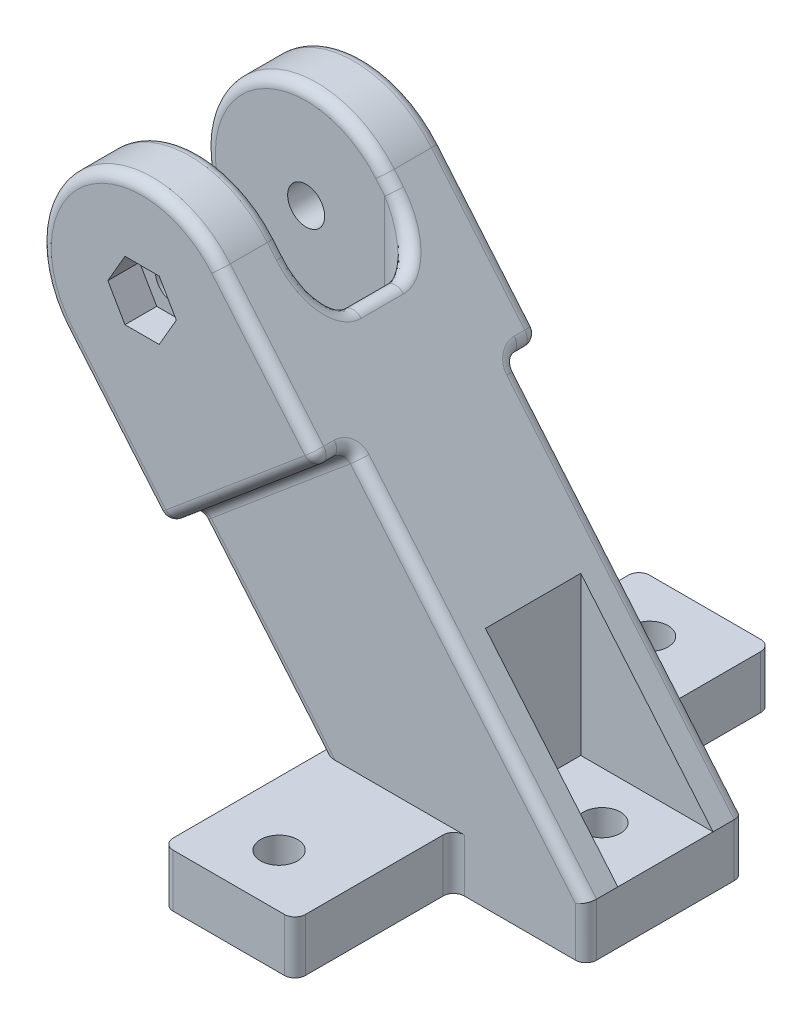
SolidWorks part; units mm, degrees
ref_plane "Alzado" through (0, 0, 0) normal (0, 0, 1) x (1, 0, 0)
ref_plane "Planta" through (0, 0, 0) normal (0, 1, 0) x (1, 0, 0)
ref_plane "Vista lateral" through (0, 0, 0) normal (1, 0, 0) x (0, 0, -1)
sketch "Croquis1" plane through (0, 0, 0) normal (0, 0, 1) x (1, 0, 0)
  line L4 (-12.5, 0) -> (12.5, 0)
  line L5 (-12.5, 0) -> (-12.5, 5)
  line L7 (12.5, 5) -> (12.5, 0)
  line L8 (-12.5, 5) -> (-50.2595, 50)
  line L9 (-50.2595, 50) -> (-25.2595, 50)
  line L10 (-25.2595, 50) -> (12.5, 5)
  line L11 (-12.5, 5) -> (-25.1154, 5) construction
  point P3 (0, 0)
  dimension "D1" = 25
  dimension "D2" = 5
  dimension "D3" = 50
  dimension "D4" = 50
  dimension "D5" = 25
extrude "Saliente-Extruir1" add sketch "Croquis1" along normal mid plane 45
sketch "Croquis3" plane through (0, 0, 0) normal (0, -1, 0) x (1, 0, 0)
  line L0 (-6.5, 0) -> (6.5, 0) construction
  line L1 (-6.5, 17.5) -> (-6.5, -17.5) construction
  circle A0 centre (-6.5, 17.5) radius 1.75
  circle A1 centre (6.5, 0) radius 1.75
  circle A2 centre (-6.5, -17.5) radius 1.75
  point P3 (0, 0)
  dimension "D3" = 3.5
  dimension "D1" = 13
  dimension "D2" = 35
extrude "Cortar-Extruir2" cut sketch "Croquis3" against normal through all
sketch "Croquis4" plane through (0, 0, 0) normal (0, -1, 0) x (1, 0, 0)
  line L0 (-12.5, 22.5) -> (12.5, 22.5) construction
  line L1 (12.5, 22.5) -> (0, 22.5)
  line L2 (12.5, 22.5) -> (12.5, 7.5)
  line L3 (12.5, 7.5) -> (0, 7.5)
  line L4 (0, 22.5) -> (0, 7.5)
  line L5 (12.5, -22.5) -> (0, -22.5)
  line L6 (12.5, -22.5) -> (12.5, -7.5)
  line L7 (12.5, -7.5) -> (0, -7.5)
  line L8 (0, -22.5) -> (0, -7.5)
  line L9 (0, 0) -> (12.5, 0) construction
  line L10 (12.5, 22.5) -> (12.5, -22.5) construction
  point P15 (0, 22.5)
  dimension "D1" = 7.5
extrude "Cortar-Extruir3" cut sketch "Croquis4" against normal through all
sketch "Croquis7" plane through (0, 50, 0) normal (0, 1, 0) x (1, 0, 0)
  line L0 (12.5, -7.5) -> (12.5, 7.5) construction
  line L1 (12.5, 4.5) -> (0, 4.5)
  line L2 (12.5, 4.5) -> (12.5, -4.5)
  line L3 (12.5, -4.5) -> (0, -4.5)
  line L4 (0, 4.5) -> (0, -4.5)
  line L5 (12.5, 7.5) -> (0, 7.5) construction
  line L7 (0, -7.5) -> (12.5, -7.5) construction
  dimension "D1" = 12.5
  dimension "D2" = 3
  dimension "D3" = 3
extrude "Cortar-Extruir6" cut sketch "Croquis7" against normal blind 45
sketch "Croquis9" plane through (9.7973, 8.2209, 0) normal (0.766, 0.6428, 0) x (0, 0, -1)
  line L1 (-22.5, 15.2419) -> (-7.5, 15.2419)
  line L2 (-22.5, 15.2419) -> (-22.5, 30.2419)
  line L3 (-22.5, 30.2419) -> (-7.5, 30.2419)
  line L4 (-7.5, 15.2419) -> (-7.5, 30.2419)
  line L5 (22.5, 15.2419) -> (7.5, 15.2419)
  line L6 (22.5, 15.2419) -> (22.5, 30.2419)
  line L7 (22.5, 30.2419) -> (7.5, 30.2419)
  line L8 (7.5, 15.2419) -> (7.5, 30.2419)
  dimension "D1" = 15
  dimension "D2" = 15
  dimension "D3" = 15
extrude "Cortar-Extruir8" cut sketch "Croquis9" against normal through all
sketch "Croquis13" plane through (-4.8733, -4.0892, 0) normal (-0.766, -0.6428, 0) x (0, 0, 1)
  line L7 (-22.5, 30.2419) -> (-7.5, 30.2419) construction
  line L8 (-22.5, 70.6084) -> (-10.5, 70.6084)
  line L9 (-22.5, 70.6084) -> (-22.5, 30.2419)
  line L10 (-22.5, 30.2419) -> (-10.5, 30.2419)
  line L11 (-10.5, 70.6084) -> (-10.5, 30.2419)
  line L12 (7.5, 30.2419) -> (22.5, 30.2419) construction
  line L13 (22.5, 70.6084) -> (10.5, 70.6084)
  line L14 (22.5, 70.6084) -> (22.5, 30.2419)
  line L15 (22.5, 30.2419) -> (10.5, 30.2419)
  line L16 (10.5, 70.6084) -> (10.5, 30.2419)
  point P0 (0, 61.014)
  dimension "D1" = 12
  dimension "D4" = 12
extrude "Cortar-Extruir11" cut sketch "Croquis13" against normal through all
sketch "Croquis15" plane through (0, 0, 0) normal (0, 0, 1) x (1, 0, 0)
  line L0 (-25.2595, 50) -> (-39.9301, 37.6899) construction
  line L1 (-50.2595, 50) -> (-24.3124, 19.0775) construction
  line L2 (-32.5948, 43.845) -> (-26.4397, 36.5097) construction
  line L3 (-25.2595, 50) -> (-9.6418, 31.3876) construction
  line L4 (-50.2595, 50) -> (-33.775, 30.3546)
  line L5 (-50.2595, 50) -> (-25.2595, 50)
  line L6 (-25.2595, 50) -> (-19.1044, 42.6647)
  arc A0 (-19.1044, 42.6647) -> (-33.775, 30.3546) centre (-26.4397, 36.5097) ccw
extrude "Cortar-Extruir12" cut sketch "Croquis15" against normal through all both and the other way through all
sketch "Croquis16" plane through (0, 0, 0) normal (0, 1, 0) x (1, 0, 0)
  line L0 (-36.0153, 10.5) -> (-36.0153, -10.5) construction
  line L1 (-36.0153, 5) -> (-16.0153, 5)
  line L2 (-36.0153, 5) -> (-36.0153, -5)
  line L3 (-36.0153, -5) -> (-16.0153, -5)
  line L4 (-16.0153, 5) -> (-16.0153, -5)
  point P6 (-16.0153, 0)
  dimension "D1" = 10
  dimension "D2" = 20
extrude "Cortar-Extruir13" cut sketch "Croquis16" along normal through all
sketch "Croquis17" plane through (0, 0, 10.5) normal (0, 0, 1) x (1, 0, 0)
  circle A0 centre (-26.4397, 36.5097) radius 1.75
  dimension "D1" = 3.5
extrude "Cortar-Extruir14" cut sketch "Croquis17" against normal through all
fillet "Redondeo2" radius 3 2 edges at (-16.0153, 24.0863, -5) (-16.0153, 24.0863, 5)
fillet "Redondeo3" radius 1 4 edges at (-16.9771, 25.2325, -10.5) (-16.9771, 25.2325, -7.5) (-16.9771, 25.2325, 10.5) (-16.9771, 25.2325, 7.5)
sketch "Croquis18" plane through (0, 0, 10.5) normal (0, 0, 1) x (1, 0, 0)
  line L0 (-32.5948, 43.845) -> (-26.4397, 36.5097) construction
  line L1 (-24.8232, 39.3097) -> (-28.0563, 39.3097)
  line L2 (-28.0563, 39.3097) -> (-29.6729, 36.5097)
  line L3 (-29.6729, 36.5097) -> (-28.0563, 33.7097)
  line L4 (-28.0563, 33.7097) -> (-24.8232, 33.7097)
  line L5 (-24.8232, 33.7097) -> (-23.2066, 36.5097)
  line L6 (-23.2066, 36.5097) -> (-24.8232, 39.3097)
  line L7 (-19.1044, 42.6647) -> (-26.4397, 36.5097) construction
  line L8 (-26.4397, 36.5097) -> (-33.775, 30.3546) construction
  line L9 (-14.6706, 7.5868) -> (0, 19.8969) construction
  circle A0 centre (-26.4397, 36.5097) radius 2.8 construction
  arc A3 (-19.1044, 42.6647) -> (-33.775, 30.3546) centre (-26.4397, 36.5097) ccw construction
  point P10 (0, 0)
  dimension "D1" = 5.6
extrude "Cortar-Extruir15" cut sketch "Croquis18" against normal blind 3
sketch "Croquis19" plane through (0, 0, 0) normal (1, 0, 0) x (0, 0, -1)
  line L1 (-22.5, 19.8969) -> (-7.5, 19.8969)
  line L2 (-22.5, 19.8969) -> (-22.5, 5)
  line L3 (-22.5, 5) -> (-7.5, 5)
  line L4 (-7.5, 19.8969) -> (-7.5, 5)
  line L5 (22.5, 19.8969) -> (7.5, 19.8969)
  line L6 (22.5, 19.8969) -> (22.5, 5)
  line L7 (22.5, 5) -> (7.5, 5)
  line L8 (7.5, 19.8969) -> (7.5, 5)
extrude "Cortar-Extruir16" cut sketch "Croquis19" against normal up to vertex (14.6706 mm away) up to point (-14.6706, 7.5868, -7.5)
fillet "Redondeo6" radius 1 42 edges at (1.7505, 17.8108, 7.5) (-9.4535, 31.1632, 7.7929) (-9.6418, 31.3876, 9) (-9.8301, 31.612, 10.2071) (-14.6945, 37.4092, 10.5) (-32.5948, 43.845, 10.5) (-18.0848, 11.6557, 7.5) (-24.1241, 18.8531, 7.7929) (-24.3124, 19.0775, 9) (-24.5007, 19.3019, 10.2071) (-18.0848, 11.6557, -7.5) (-24.1241, 18.8531, -7.7929) (-24.3124, 19.0775, -9) (-24.5007, 19.3019, -10.2071) (1.7505, 17.8108, -7.5) (-9.4535, 31.1632, -7.7929) (-9.6418, 31.3876, -9) (-9.8301, 31.612, -10.2071) (-14.6945, 37.4092, -10.5) (-32.5948, 43.845, -10.5) (-12.5, 2.5, -22.5) (0, 2.5, -22.5) (0, 2.5, -7.5) (12.5, 2.5, -7.5) (12.5, 2.5, 7.5) (0, 2.5, 7.5) (-12.5, 2.5, 22.5) (0, 2.5, 22.5) (-29.3651, 25.0991, 10.5) (-29.3651, 25.0991, -10.5) (-32.5948, 43.845, -5) (-19.0599, 42.6116, -5) (-16.894, 40.0304, -4.1213) (-16.0153, 38.9832, 0) (-16.894, 40.0304, 4.1213) (-19.0599, 42.6116, 5) (-32.5948, 43.845, 5) (-26.3952, 21.5596, 5) (-16.894, 10.2365, 4.1213) (-16.0153, 9.1894, 0) (-16.894, 10.2365, -4.1213) (-26.3952, 21.5596, -5)
